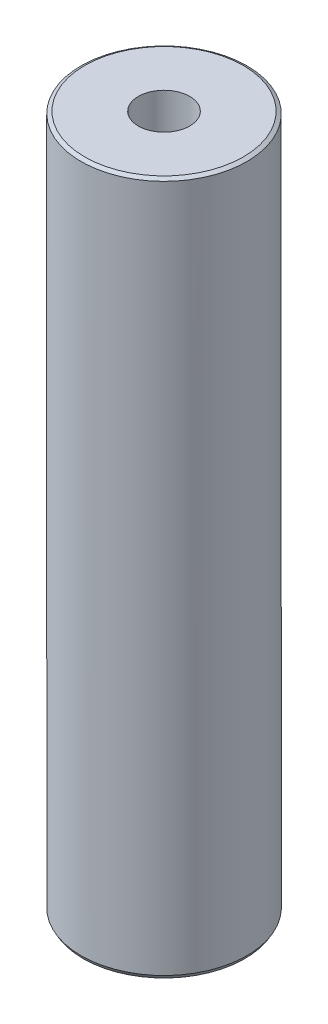
SolidWorks part; units mm, degrees
ref_plane "Front Plane" through (0, 0, 0) normal (0, 0, 1) x (1, 0, 0)
ref_plane "Top Plane" through (0, 0, 0) normal (0, 1, 0) x (1, 0, 0)
ref_plane "Right Plane" through (0, 0, 0) normal (1, 0, 0) x (0, 0, -1)
sketch "Sketch1" plane through (0, 0, 0) normal (0, 1, 0) x (1, 0, 0)
  circle A0 centre (0, 0) radius 30
  dimension "SHAFT_OD" = 60
extrude "Boss-Extrude1" add sketch "Sketch1" along normal blind 250.8427
sketch "Sketch2" plane through (0, 0, 0) normal (0, 1, 0) x (1, 0, 0)
  circle A0 centre (0, 0) radius 9.293
  dimension "BORE_D" = 18.5861
extrude "Cut-Extrude1" cut sketch "Sketch2" along normal through all
chamfer "Chamfer1" distance 0.7673 angle 60 2 edges at (0, 250.8427, 30) (0, 0, 30) first distance on face at (0, 250.8427, 30) first distance on face at (0, 0, 9.293)
